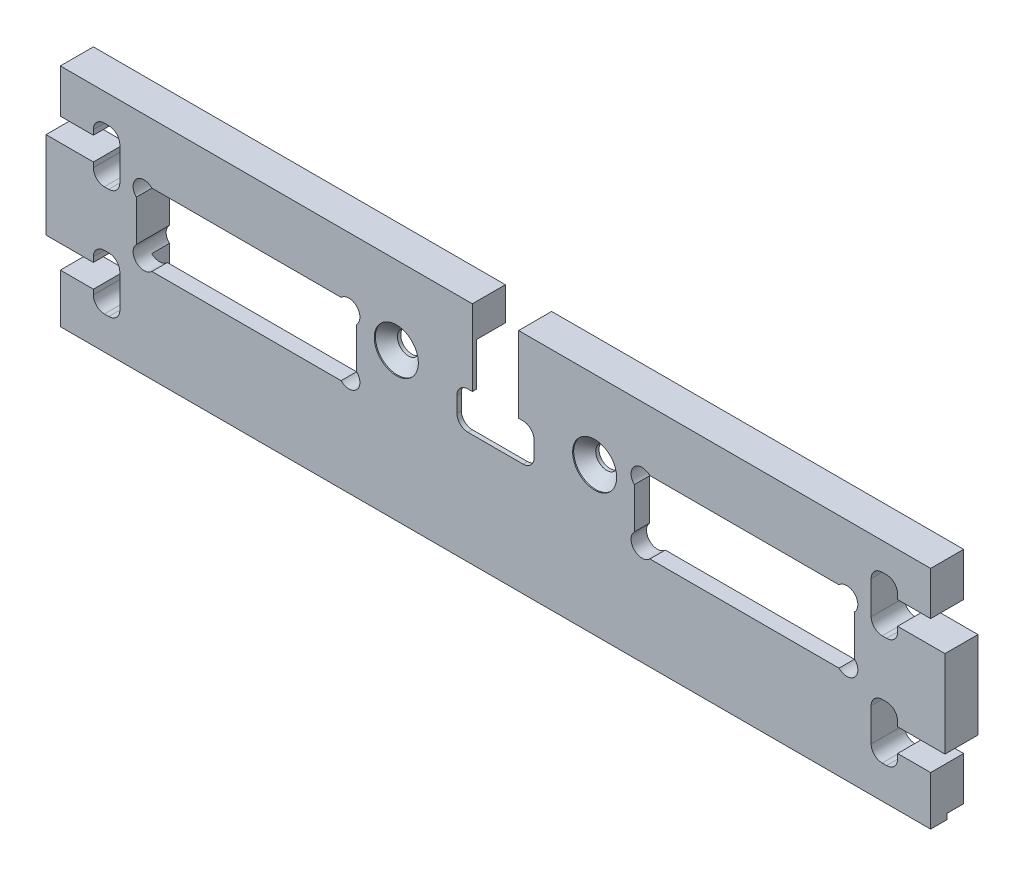
SolidWorks part; units mm, degrees
ref_plane "Front Plane" through (0, 0, 0) normal (0, 0, 1) x (1, 0, 0)
ref_plane "Top Plane" through (0, 0, 0) normal (0, 1, 0) x (1, 0, 0)
ref_plane "Right Plane" through (0, 0, 0) normal (1, 0, 0) x (0, 0, -1)
sketch "Sketch1" plane through (0, 0, 0) normal (0, 0, 1) x (1, 0, 0)
  line L0 (-39.5, 0) -> (39.5, 0) construction
  line L1 (-39.5, 10) -> (39.5, 10)
  line L2 (-39.5, 10) -> (-39.5, -10)
  line L3 (-39.5, -10) -> (39.5, -10)
  line L4 (39.5, 10) -> (39.5, -10)
  line L5 (-39.5, 10) -> (39.5, -10) construction
  line L6 (-39.5, -10) -> (39.5, 10) construction
  line L7 (0, 10) -> (0, -10) construction
  line L9 (-40.8, -3.95) -> (-39.5, -3.95)
  line L10 (-40.8, -3.95) -> (-40.8, 3.95)
  line L11 (-40.8, 3.95) -> (-39.5, 3.95)
  line L12 (-39.5, -3.95) -> (-39.5, 3.95)
  line L13 (-40.8, -3.95) -> (-39.5, 3.95) construction
  line L14 (-40.8, 3.95) -> (-39.5, -3.95) construction
  line L16 (40.8, 3.95) -> (39.5, 3.95)
  line L17 (40.8, -3.95) -> (40.8, 3.95)
  line L18 (40.8, -3.95) -> (39.5, -3.95)
  line L19 (-39.5, 5) -> (39.5, 5) construction
  line L20 (-35.3, 7.5) -> (-35.3, 2.5) construction
  line L21 (-36.5, 3.95) -> (-39.5, 3.95)
  line L22 (-36.5, 3.95) -> (-36.5, 6.05)
  line L23 (-36.5, 6.05) -> (-39.5, 6.05)
  line L24 (-39.5, 3.95) -> (-39.5, 6.05)
  line L25 (-36.5, 3.95) -> (-39.5, 6.05) construction
  line L26 (-36.5, 6.05) -> (-39.5, 3.95) construction
  line L27 (-34.1, 7.5) -> (-36.5, 7.5)
  line L28 (-34.1, 7.5) -> (-34.1, 2.5)
  line L29 (-34.1, 2.5) -> (-36.5, 2.5)
  line L30 (-36.5, 7.5) -> (-36.5, 2.5)
  line L31 (-34.1, 7.5) -> (-36.5, 2.5) construction
  line L32 (-34.1, 2.5) -> (-36.5, 7.5) construction
  line L33 (-34.1, -7.5) -> (-36.5, -7.5)
  line L34 (-34.1, -7.5) -> (-34.1, -2.5)
  line L35 (-34.1, -2.5) -> (-36.5, -2.5)
  line L36 (-36.5, -7.5) -> (-36.5, -2.5)
  line L37 (-36.5, -3.95) -> (-39.5, -3.95)
  line L38 (-36.5, -6.05) -> (-39.5, -6.05)
  line L39 (36.5, 3.95) -> (39.5, 3.95)
  line L40 (36.5, 6.05) -> (39.5, 6.05)
  line L41 (36.5, 7.5) -> (36.5, 2.5)
  line L42 (34.1, 7.5) -> (36.5, 7.5)
  line L43 (34.1, 7.5) -> (34.1, 2.5)
  line L44 (34.1, 2.5) -> (36.5, 2.5)
  line L45 (34.1, -2.5) -> (36.5, -2.5)
  line L46 (34.1, -7.5) -> (34.1, -2.5)
  line L47 (34.1, -7.5) -> (36.5, -7.5)
  line L48 (36.5, -7.5) -> (36.5, -2.5)
  line L49 (36.5, -6.05) -> (39.5, -6.05)
  line L50 (36.5, -3.95) -> (39.5, -3.95)
  point P0 (0, 0)
  point P10 (-40.15, 0)
  point P15 (-38, 5)
  point P35 (-35.3, 5)
  dimension "D1" = 79
  dimension "D2" = 20
  dimension "D4" = 1.3
  dimension "D7" = 5
  dimension "D8" = 2.1
  dimension "D9" = 3
  dimension "D10" = 2.4
  dimension "D11" = 5
extrude "Base shape" add sketch "Sketch1" along normal blind 3 contours L4 L1 L2 L3 | L9 L2 L11 L10 | L16 L4 L18 L17 region at (0, 0, 0) region at (-40.15, 0, 0) region at (40.15, 0, 0)
sketch "Sketch4" plane through (0, -10, 0) normal (0, -1, 0) x (1, 0, 0)
  line L0 (39.5, 3) -> (39.5, 0) construction
  line L1 (-39.5, 3) -> (39.5, 3)
  line L2 (-39.5, 3) -> (-39.5, 1.5)
  line L3 (-39.5, 1.5) -> (39.5, 1.5)
  line L4 (39.5, 3) -> (39.5, 1.5)
extrude "Floor lip" add sketch "Sketch4" along normal blind 0.5
sketch "Sketch6" plane through (0, 0, 0) normal (0, 0, -1) x (-1, 0, 0)
  line L0 (0, 0) -> (0, -10) construction
  line L1 (39.5, -10) -> (-39.5, -10) construction
  line L2 (-4, -10) -> (4, -10) construction
  line L3 (39.5, -10) -> (-39.5, -10) construction
  line L4 (-4, -9) -> (4, -9)
  line L5 (-4, -11) -> (4, -11)
  arc A0 (-4, -9) -> (-4, -11) centre (-4, -10) ccw
  arc A1 (4, -11) -> (4, -9) centre (4, -10) ccw
  point P9 (0, -10)
  dimension "D1" = 2
  dimension "D2" = 8
extrude "Nail cutout" cut sketch "Sketch6" against normal up to surface (1.5 mm away) up to face at (0, -10.25, 1.5)
sketch "Sketch3" plane through (-40.8, 0, 0) normal (-1, 0, 0) x (0, 0, 1)
  line L0 (0, 6.05) -> (3, 3.95) construction
  line L1 (0, 6.05) -> (3, 6.05)
  line L2 (0, 6.05) -> (0, 3.95)
  line L3 (0, 3.95) -> (3, 3.95)
  line L4 (3, 6.05) -> (3, 3.95)
  line L5 (0, -3.95) -> (3, -6.05) construction
  line L6 (0, -3.95) -> (3, -3.95)
  line L7 (0, -3.95) -> (0, -6.05)
  line L8 (0, -6.05) -> (3, -6.05)
  line L9 (3, -3.95) -> (3, -6.05)
  point P6 (1.5, 5)
  point P13 (1.5, -5)
ref_axis "Tap axis top" through (-53.7846, 5, 1.5) along (1, 0, 0)
ref_axis "Tap axis bottom" through (-54.2844, -5, 1.5) along (1, 0, 0)
fillet "Mill fillets" radius 1 16 edges at (36.5, -7.5, 1.5) (36.5, 2.5, 1.5) (34.1, 2.5, 1.5) (34.1, -7.5, 1.5) (36.5, -2.5, 1.5) (36.5, 7.5, 1.5) (34.1, -2.5, 1.5) (34.1, 7.5, 1.5) (-36.5, -2.5, 1.5) (-34.1, -2.5, 1.5) (-34.1, -7.5, 1.5) (-36.5, -7.5, 1.5) (-36.5, 2.5, 1.5) (-34.1, 2.5, 1.5) (-34.1, 7.5, 1.5) (-36.5, 7.5, 1.5)
sketch "Sketch8" [suppressed] plane through (0, 0, 3) normal (0, 0, 1) x (1, 0, 0)
  line L0 (-40.8, 0) -> (40.8, 0) construction
  line L1 (-40.8, -3.95) -> (-40.8, 3.95) construction
  line L2 (40.8, -3.95) -> (40.8, 3.95) construction
  line L4 (-24.5, 5.15) -> (24.5, 5.15)
  line L5 (-25.5, 4.15) -> (-25.5, -4.15)
  line L6 (-24.5, -5.15) -> (24.5, -5.15)
  line L7 (25.5, 4.15) -> (25.5, -4.15)
  line L8 (-25.5, 5.15) -> (25.5, -5.15) construction
  line L9 (-25.5, -5.15) -> (25.5, 5.15) construction
  arc A0 (24.5, -5.15) -> (25.5, -4.15) centre (24.5, -4.15) ccw
  arc A1 (24.5, 5.15) -> (25.5, 4.15) centre (24.5, 4.15) cw
  arc A2 (-25.5, -4.15) -> (-24.5, -5.15) centre (-24.5, -4.15) ccw
  arc A3 (-24.5, 5.15) -> (-25.5, 4.15) centre (-24.5, 4.15) ccw
  point P6 (0, 0)
  dimension "D3" = 1
  dimension "D1" = 51
  dimension "D2" = 10.3
extrude "Led strip pocket" [suppressed] cut sketch "Sketch8" against normal offset from surface (2.5 mm away) 0.5 up to face at (0, -0.6712, 0)
sketch "Sketch9" [suppressed] plane through (0, 0, 0.5) normal (0, 0, 1) x (1, 0, 0)
  line L0 (-19.5, 5.15) -> (-19.5, -5.15)
  line L1 (0, 5.15) -> (0, -5.15) construction
  line L2 (19.5, 5.15) -> (19.5, -5.15)
  line L3 (-25.5, -2.978) -> (25.5, -2.978) construction
  line L4 (25.5, -4.15) -> (25.5, 4.15)
  line L5 (24.5, 5.15) -> (-24.5, 5.15)
  line L6 (-25.5, 4.15) -> (-25.5, -4.15)
  line L7 (-24.5, -5.15) -> (24.5, -5.15)
  line L8 (25.5, -4.15) -> (25.5, 4.15)
  line L9 (24.5, 5.15) -> (-24.5, 5.15)
  line L10 (-25.5, 4.15) -> (-25.5, -4.15)
  line L11 (-24.5, -5.15) -> (24.5, -5.15)
  circle A0 centre (-12.7, -2.978) radius 1
  circle A1 centre (12.7, -2.978) radius 1
  arc A4 (24.5, -5.15) -> (25.5, -4.15) centre (24.5, -4.15) ccw
  arc A5 (25.5, 4.15) -> (24.5, 5.15) centre (24.5, 4.15) ccw
  arc A6 (-24.5, 5.15) -> (-25.5, 4.15) centre (-24.5, 4.15) ccw
  arc A7 (-25.5, -4.15) -> (-24.5, -5.15) centre (-24.5, -4.15) ccw
  arc A8 (24.5, -5.15) -> (25.5, -4.15) centre (24.5, -4.15) ccw
  arc A9 (25.5, 4.15) -> (24.5, 5.15) centre (24.5, 4.15) ccw
  arc A10 (-24.5, 5.15) -> (-25.5, 4.15) centre (-24.5, 4.15) ccw
  arc A11 (-25.5, -4.15) -> (-24.5, -5.15) centre (-24.5, -4.15) ccw
  arc M13 (24.5, -5.15) -> (25.5, -4.15) centre (24.5, -4.15) ccw
  line M14 (25.5, -4.15) -> (25.5, 4.15)
  arc M15 (25.5, 4.15) -> (24.5, 5.15) centre (24.5, 4.15) ccw
  line M16 (24.5, 5.15) -> (-24.5, 5.15)
  arc M17 (-24.5, 5.15) -> (-25.5, 4.15) centre (-24.5, 4.15) ccw
  line M18 (-25.5, 4.15) -> (-25.5, -4.15)
  arc M19 (-25.5, -4.15) -> (-24.5, -5.15) centre (-24.5, -4.15) ccw
  line M20 (-24.5, -5.15) -> (24.5, -5.15)
  dimension "D4" = 2
  dimension "D2" = 6
  dimension "D3" = 8.128
  dimension "D5" = 25.4
  dimension "D1" = 0
extrude "Led strip cuts" [suppressed] cut sketch "Sketch9" against normal up to next contours L0 M16 M17 M18 M19 M20 | L2 M16 M20 M13 M14 M15 | A0 | A1
fillet "Led strip cut fillets" [suppressed] radius 1
sketch "Sketch13" plane through (0, 0, 0) normal (0, 0, -1) x (-1, 0, 0)
  line L0 (0, 15.8648) -> (0, -21.9195) construction
  line L2 (-4.1, -5.7) -> (4.1, -5.7)
  line L3 (-5.1, -4.7) -> (-5.1, 6)
  line L4 (-4.1, 7) -> (4.1, 7)
  line L5 (5.1, -4.7) -> (5.1, 6)
  line L6 (-5.1, -5.7) -> (5.1, 7) construction
  line L7 (-5.1, 7) -> (5.1, -5.7) construction
  line L10 (39.5, 10) -> (-39.5, 10) construction
  arc A0 (-4.1, -5.7) -> (-5.1, -4.7) centre (-4.1, -4.7) cw
  arc A1 (4.1, -5.7) -> (5.1, -4.7) centre (4.1, -4.7) ccw
  arc A4 (5.1, 6) -> (4.1, 7) centre (4.1, 6) ccw
  arc A5 (-5.1, 6) -> (-4.1, 7) centre (-4.1, 6) cw
  point P1 (0, 0.65)
  point P8 (0, 0)
  point P9 (5.5684, 9.0125)
  point P16 (0, 0)
  point P17 (0, 0)
  dimension "D4" = 1
  dimension "D5" = 1
  dimension "D1" = 10.2
  dimension "D2" = 12.7
  dimension "D3" = 3
extrude "Bumper mount inner cut" cut sketch "Sketch13" against normal offset from surface (2.6 mm away) 0.4 up to face at (0, -0.0192, 3)
sketch "Sketch14" plane through (0, 0, 0) normal (0, 0, -1) x (-1, 0, 0)
  line L1 (0, 12.9528) -> (0, -14.0841) construction
  line L2 (4.1, 7) -> (-4.1, 7) construction
  line L3 (-4.1, -5.7) -> (4.1, -5.7) construction
  line L4 (-11.6, 7) -> (11.6, 7)
  line L5 (-12.6, 6) -> (-12.6, -4.7)
  line L6 (-11.6, -5.7) -> (11.6, -5.7)
  line L7 (12.6, 6) -> (12.6, -4.7)
  line L8 (-12.6, 7) -> (12.6, -5.7) construction
  line L9 (-12.6, -5.7) -> (12.6, 7) construction
  arc A1 (11.6, -5.7) -> (12.6, -4.7) centre (11.6, -4.7) ccw
  arc A2 (-12.6, -4.7) -> (-11.6, -5.7) centre (-11.6, -4.7) ccw
  arc A3 (11.6, 7) -> (12.6, 6) centre (11.6, 6) cw
  arc A4 (-12.6, 6) -> (-11.6, 7) centre (-11.6, 6) cw
  point P6 (0, 0.65)
  dimension "D2" = 1
  dimension "D3" = 1
  dimension "D1" = 25.2
extrude "Bumper mount outer cut" cut sketch "Sketch14" against normal blind 1.6
sketch "Sketch15" plane through (0, 0, 1.6) normal (0, 0, -1) x (-1, 0, 0)
  line L0 (-12.6, 2.9) -> (12.6, 2.9) construction
  line L3 (0, 16.4744) -> (0, -20.0474) construction
  line L7 (-12.6, 6) -> (-12.6, -4.7) construction
  line L8 (12.6, -4.7) -> (12.6, 6) construction
  line L11 (-4.1, 7) -> (-11.6, 7) construction
  circle A0 centre (-9, 2.9) radius 1
  circle A1 centre (9, 2.9) radius 1
  point P5 (10, 7)
  point P13 (0, 0)
  point P19 (0, 0)
  point P22 (0, 0)
  point P24 (0, 0)
  point P25 (8.6174, -5.7)
  point P26 (0, 0)
  point P27 (0, 0)
  point P28 (0, 0)
  point P29 (0, 0)
  point P30 (13.4221, 7)
  dimension "D1" = 18
  dimension "D2" = 2
  dimension "D3" = 4.1
extrude "Bumper mount screw holes" cut sketch "Sketch15" against normal up to next
sketch "Sketch16" plane through (0, 0, 2.6) normal (0, 0, -1) x (-1, 0, 0)
  line L0 (-5.1, 1.4) -> (5.1, 1.4) construction
  line L3 (0, 7) -> (0, -4.2) construction
  line L4 (-2.5, 3.1) -> (2.5, 3.1)
  line L5 (-3.5, 2.1) -> (-3.5, 0.7)
  line L6 (-2.5, -0.3) -> (2.5, -0.3)
  line L7 (3.5, 2.1) -> (3.5, 0.7)
  line L8 (-3.5, 3.1) -> (3.5, -0.3) construction
  line L9 (-3.5, -0.3) -> (3.5, 3.1) construction
  line L11 (-5.1, 6) -> (-5.1, -4.7) construction
  line L13 (4.1, 7) -> (-4.1, 7) construction
  arc A0 (2.5, -0.3) -> (3.5, 0.7) centre (2.5, 0.7) ccw
  arc A1 (-3.5, 0.7) -> (-2.5, -0.3) centre (-2.5, 0.7) ccw
  arc A2 (-2.5, 3.1) -> (-3.5, 2.1) centre (-2.5, 2.1) ccw
  arc A3 (2.5, 3.1) -> (3.5, 2.1) centre (2.5, 2.1) cw
  point P2 (0, 0)
  point P5 (0, 0)
  point P6 (0, 1.4)
  point P23 (0, 0)
  point P24 (0, 7.9459)
  point P29 (0, 0)
  dimension "D3" = 1
  dimension "D1" = 7
  dimension "D2" = 3.4
  dimension "D4" = 11.2
extrude "Bumper body cut" cut sketch "Sketch16" against normal up to next
hole_wizard "Bumper screw countersunks" positions "Sketch17" profile "Sketch18" countersink size "M2" standard "ANSI Metric" end condition through all
sketch "Sketch17" plane through (0, 0, 3) normal (0, 0, 1) x (1, 0, 0)
  point P0 (9, 2.9)
  point P3 (-9, 2.9)
sketch "Sketch18" plane through (9, 2.9, 3) normal (1, 0, 0) x (0, -1, 0)
  line L0 (0, 0) -> (0, 3)
  line L1 (0, 3) -> (1, 3)
  line L2 (1, 3) -> (1, 1.1)
  line L3 (1, 1.1) -> (2, 0.1)
  line L4 (2, 0.1) -> (2, 0)
  line L6 (2, 0) -> (0, 0)
  line L7 (-1, 1.1) -> (-2, 0.1) construction
  line L11 (0, -6.35) -> (0, 107.95) construction
  dimension "Thru Hole Dia." = 2
  dimension "Thru Hole Depth" = 3
  dimension "C'Sink Dia." = 4
  dimension "C'Sink Angle" = 90
  dimension "Head Clearance" = 0.1
sketch "Sketch19" plane through (0, 0, 0) normal (0, 0, -1) x (-1, 0, 0)
  line L0 (0, 15.6498) -> (0, -12.9575) construction
  line L1 (39.5, 10) -> (-39.5, 10) construction
  line L2 (-2.1, 3.1) -> (2.1, 3.1)
  line L3 (-2.1, 3.1) -> (-2.1, 10)
  line L4 (-2.1, 10) -> (2.1, 10)
  line L5 (2.1, 3.1) -> (2.1, 10)
  line L6 (-2.1, 3.1) -> (2.1, 10) construction
  line L7 (-2.1, 10) -> (2.1, 3.1) construction
  line L8 (2.5, 3.1) -> (-2.5, 3.1) construction
  point P1 (0, 6.55)
  dimension "D1" = 4.2
extrude "Bumper insertion cut" cut sketch "Sketch19" against normal up to next
sketch "Sketch20" plane through (0, 0, 0) normal (0, 0, -1) x (-1, 0, 0)
  line L0 (-12.6, 6) -> (-12.6, -4.7) construction
  line L1 (-12.6, 4.55) -> (-32.6, 4.55)
  line L2 (-12.6, 4.55) -> (-12.6, -2)
  line L3 (-12.6, -2) -> (-32.6, -2)
  line L4 (-32.6, 4.55) -> (-32.6, -2)
  line L5 (-2.1, 10) -> (-39.5, 10) construction
  line L6 (-12.6, 4.55) -> (-19.15, -2) construction
  line L7 (-22.6, 4.55) -> (-22.6, -2) construction
  line L8 (-32.6, 1.275) -> (-12.6, 1.275) construction
  line L9 (0, 16.176) -> (0, -15.99) construction
  line L10 (12.6, 4.55) -> (12.6, -2)
  line L11 (12.6, -2) -> (32.6, -2)
  line L12 (32.6, 4.55) -> (32.6, -2)
  line L13 (12.6, 4.55) -> (32.6, 4.55)
  circle A0 centre (-13.3071, 3.8429) radius 1
  circle A1 centre (-31.8929, 3.8429) radius 1
  circle A2 centre (-13.3071, -1.2929) radius 1
  circle A3 centre (-31.8929, -1.2929) radius 1
  circle A4 centre (13.3071, 3.8429) radius 1
  circle A5 centre (13.3071, -1.2929) radius 1
  circle A6 centre (31.8929, -1.2929) radius 1
  circle A7 centre (31.8929, 3.8429) radius 1
  dimension "D5" = 2
  dimension "D1" = 20
  dimension "D2" = 5.45
  dimension "D3" = 6.55
  dimension "D4" = 45
extrude "Bumper switches cut" cut sketch "Sketch20" against normal up to next contours L1 L4 L3 L2 | A1 | A3 | A0 | A2 | L13 L12 L11 L10 | A4 | A5 | A6 | A7
sketch "Sketch21" plane through (0, 0, 0) normal (0, 0, -1) x (-1, 0, 0)
  line L0 (-14.0142, -2) -> (-31.1858, -2) construction
  line L1 (-32.6, -2) -> (-12.6, -2)
  line L2 (-32.6, -2) -> (-32.6, -5.7)
  line L3 (-32.6, -5.7) -> (-12.6, -5.7)
  line L4 (-12.6, -2) -> (-12.6, -5.7)
  line L5 (-12.6, -2) -> (-12.6, -4.7) construction
  line L6 (-11.6, -5.7) -> (-4.1, -5.7) construction
  line L7 (-32.6, 3.1358) -> (-32.6, -0.5858) construction
  line L8 (-12.6, -5.7) -> (-11.6, -5.7)
  line L9 (-32.6, -5.7) -> (-28.9, -2) construction
  line L10 (0, 14.2019) -> (0, -15.3745) construction
  line L11 (12.6, -5.7) -> (11.6, -5.7)
  line L12 (12.6, -2) -> (12.6, -5.7)
  line L13 (32.6, -2) -> (12.6, -2)
  line L14 (32.6, -2) -> (32.6, -5.7)
  line L15 (32.6, -5.7) -> (12.6, -5.7)
  arc A0 (-12.6, -4.7) -> (-11.6, -5.7) centre (-11.6, -4.7) ccw construction
  arc A1 (-12.6, -4.7) -> (-11.6, -5.7) centre (-11.6, -4.7) ccw
  circle A2 centre (-31.8929, -4.9929) radius 1
  arc A3 (-32.6, -0.5858) -> (-31.1858, -2) centre (-31.8929, -1.2929) ccw construction
  circle A4 centre (31.8929, -4.9929) radius 1
  arc A5 (12.6, -4.7) -> (11.6, -5.7) centre (11.6, -4.7) cw
  dimension "D1" = 45
extrude "Bumper switch mounts cut" cut sketch "Sketch21" against normal up to surface (1.6 mm away) contours A1 L4 L8 | L12 A5 L11 | L4 L1 L2 L3 | A2 | L12 L13 L14 L15 | A4 region at (12.3766, -5.4766, 0) region at (-12.3766, -5.4766, 0) up to face at (-8, 2.9, 1.6)
